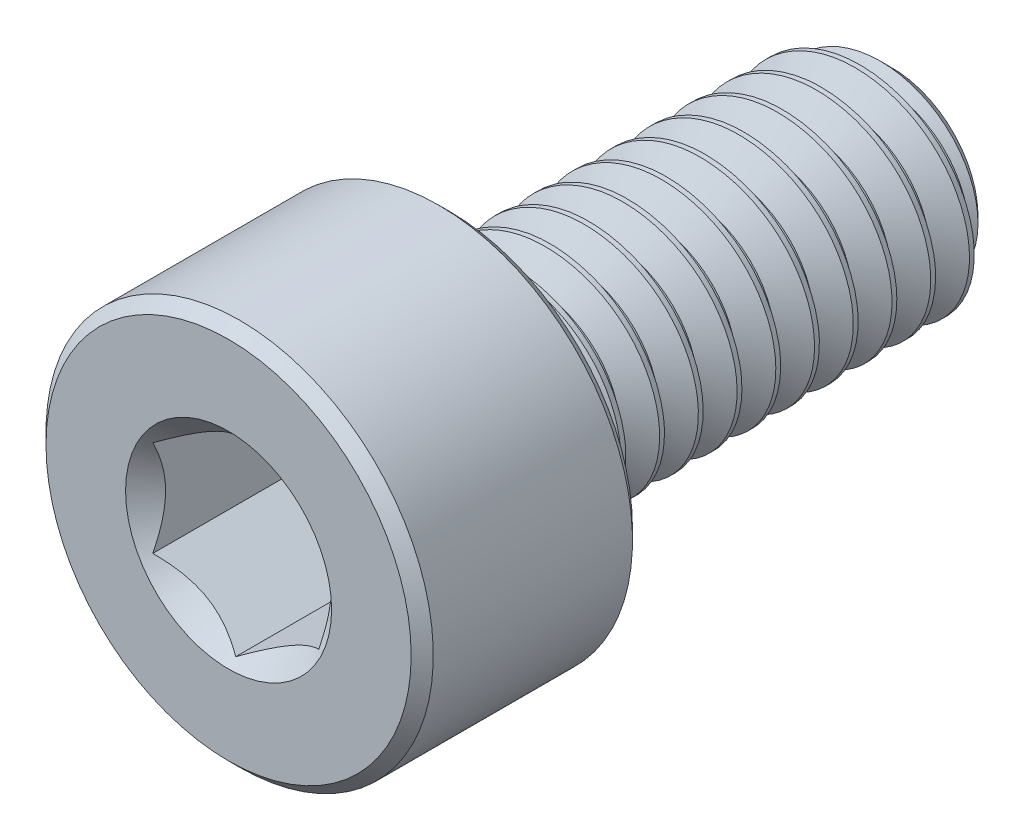
SolidWorks part; units mm, degrees
ref_plane "Front Plane" through (0, 0, 0) normal (0, 0, 1) x (1, 0, 0)
ref_plane "Top Plane" through (0, 0, 0) normal (0, 1, 0) x (1, 0, 0)
ref_plane "Right Plane" through (0, 0, 0) normal (1, 0, 0) x (0, 0, -1)
sketch "Sketch1" plane through (0, 0, 0) normal (1, 0, 0) x (0, 0, -1)
  line L0 (-6, 0) -> (6, 0) construction
  line L1 (6, 0) -> (6, 1.5453) construction
  line L2 (6, 1.5453) -> (5.5453, 2) construction
  line L3 (5.5453, 2) -> (5.475, 2) construction
  line L4 (5.475, 2) -> (-2, 2) construction
  line L5 (-2, 2) -> (-2, 3.5) construction
  line L6 (-2, 3.5) -> (-6, 3.5) construction
  line L7 (-6, 3.5) -> (-6, 0) construction
  line L8 (6, 1.5453) -> (6, 2) construction
  line L9 (5.9562, 2.0758) -> (6.3062, 1.4696) construction
  line L10 (6.3062, 1.4696) -> (6.6562, 2.0758) construction
  line L11 (6.6562, 2.0758) -> (5.9562, 2.0758) construction
  line L12 (6.3062, 2.0758) -> (6.3063, 2) construction
  line L13 (6.3062, 1.4696) -> (6.3062, 1.5453) construction
  line L14 (6.2625, 1.5453) -> (6.35, 1.5453) construction
  line L15 (6, 2) -> (6.6125, 2) construction
  line L16 (5.9781, 2.0379) -> (6.6344, 2.0379) construction
  line L17 (6, 0) -> (6, -2) construction
  line L18 (-2.2, 3.5) -> (-2, 3.3) construction
  line L19 (-5.8, 3.5) -> (-6, 3.3) construction
  line L20 (-2, 2) -> (-2, 0) construction
  line L21 (-2, 1) -> (0.6667, 1) construction
  line L22 (0.6667, 1) -> (3.3333, 1) construction
  line L23 (3.3333, 1) -> (6, 1) construction
  line L24 (0.6667, 1) -> (0.6667, 2) construction
  line L25 (0.6667, 2) -> (0.6667, 3.5) construction
  line L26 (3.3333, 1) -> (3.3333, 3.5) construction
  point P0 (-6, 1.5)
  point P3 (4.25, 2)
  point P4 (0, 0)
  point P18 (3.3333, 2)
  point P22 (6.3062, 1.5453)
  point P24 (5.475, 2)
  point P25 (6.3063, 2)
  point P28 (6.3063, 2.0379)
  point P29 (4.25, -2)
  point P30 (0.6667, 2)
  point P31 (-4, 3.5)
  point P37 (-2.7, 3.5)
  point P38 (-5.7, 3.5)
  point P45 (0.6667, 1)
  point P46 (3.3333, 1)
  dimension "D2" = 0.0875
  dimension "D7" = 0.2
  dimension "D8" = 0.2
  dimension "D9" = 0.2
  dimension "D10" = 0.1
  dimension "D11" = 0.5
  dimension "Drive Size" = 3
  dimension "Head Diameter" = 7
  dimension "Head Height" = 4
  dimension "Thread Pitch" = 0.7
  dimension "Thread Size" = 4
  dimension "Length" = 8
  dimension "D12" = 0.525
  dimension "D4" = 1.75
  dimension "D3" = 45
sketch "Sketch2" plane through (0, 0, 0) normal (1, 0, 0) x (0, 0, -1)
  line L0 (-6, 0) -> (-6, 3.3)
  line L1 (-5.8, 3.5) -> (-2.2, 3.5)
  line L2 (-2, 3.3) -> (-2, 2.2)
  line L4 (5.5453, 2) -> (6, 1.5453)
  line L5 (6, 1.5453) -> (6, 0)
  line L6 (-2, 3.5) -> (-6, 3.5) construction
  line L7 (6, 0) -> (-6, 0)
  line L8 (-5.8, 3.5) -> (-6, 3.3) construction
  line L10 (-5.8, 3.5) -> (-6, 3.3)
  line L14 (-2.2, 3.5) -> (-2, 3.3) construction
  line L16 (-2.2, 3.5) -> (-2, 3.3)
  line L17 (-2, 2) -> (-2, 3.5) construction
  line L19 (-1.8, 2) -> (5.5453, 2)
  line L20 (5.475, 2) -> (-2, 2) construction
  arc A1 (-2, 2.2) -> (-1.8, 2) centre (-1.8, 2.2) ccw
  dimension "D3" = 0.2
revolve "Revolve1" add sketch "Sketch2" angle 360 about L7
sketch "Sketch3" plane through (0, 0, 6) normal (0, 0, 1) x (1, 0, 0)
  line L1 (1.5, -0.866) -> (1.5, 0.866)
  line L2 (1.5, 0.866) -> (0, 1.7321)
  line L3 (0, 1.7321) -> (-1.5, 0.866)
  line L4 (-1.5, 0.866) -> (-1.5, -0.866)
  line L5 (-1.5, -0.866) -> (0, -1.7321)
  line L6 (0, -1.7321) -> (1.5, -0.866)
  circle A0 centre (0, 0) radius 1.5 construction
  circle A1 centre (0, 0) radius 3.5 construction
  circle A2 centre (0, 0) radius 3.5 construction
  circle A3 centre (0, 0) radius 1.7321 construction
  point P13 (0, 0)
  dimension "D1" = 3.4641
extrude "Cut-Extrude1" cut sketch "Sketch3" against normal offset from surface (3 mm away) 1 up to face at (0, 3.3, 2)
sketch "Sketch4" plane through (0, 0, 6) normal (0, 0, 1) x (1, 0, 0)
  circle A0 centre (0, 0) radius 1.862
  dimension "D1" = 3.7239
extrude "Cut-Extrude2" cut sketch "Sketch4" against normal up to vertex (2 mm away) draft 45 up to point (0, 3.5, 4)
sketch "Sketch11" plane through (0, 0, 0) normal (1, 0, 0) x (0, 0, -1)
  line L0 (-6, 0) -> (6, 0) construction
  line L1 (-6, 0) -> (6, 0) construction
  line L2 (-0.5, 0) -> (-0.5, 2) construction
  line L3 (5.475, 2) -> (-2, 2) construction
  line L4 (4.5, 0) -> (4.5, 2) construction
  line L6 (6, 1.5453) -> (6, 2) construction
  point P2 (-0.5, 0)
  point P3 (4.5, 0)
  dimension "D1" = 1.5
  dimension "D2" = 1.5
sketch "Sketch6" plane through (0, 0, -6) normal (0, 0, -1) x (-1, 0, 0)
  circle A0 centre (0, 0) radius 2
curve "Helix/Spiral1" pitch 0.7 height 8.7 radius 2 centre (0, 0, -6) axis (0, 0, 1) start towards (0, 1, 0)
sketch "Sketch10" plane through (0, 0, 0) normal (1, 0, 0) x (0, 0, -1)
  line L0 (-1.8, -3.5) -> (-1.8, 3.5)
  line L5 (-6, 0) -> (6, 0) construction
  line L6 (-1.8, 2) -> (-1.8, -2) construction
  point P3 (-1.8, 0)
split "Split1" trim tools "Sketch10" bodies to split 106 resulting bodies 114 115
sketch "Sketch7" plane through (0, 0, 0) normal (1, 0, 0) x (0, 0, -1)
  line L0 (5.9781, 2.0379) -> (6.6344, 2.0379)
  line L1 (6.6344, 2.0379) -> (6.35, 1.5453)
  line L2 (6.35, 1.5453) -> (6.2625, 1.5453)
  line L3 (6.2625, 1.5453) -> (5.9781, 2.0379)
sweep "Cut-Sweep1" cut profiles "Sketch7" path "Helix/Spiral1" align with end faces yes
sketch "Sketch8" plane through (0, 0, 0) normal (1, 0, 0) x (0, 0, -1)
  line L0 (-2, 0) -> (-2, 2)
  line L1 (-1.8, -2) -> (-1.8, 2) construction
  line L2 (-2, 2) -> (-1.8, 2)
  line L4 (-1.8, 2) -> (-0.6453, 0)
  line L5 (-0.6453, 0) -> (-2, 0)
  line L6 (5.475, 2) -> (-2, 2) construction
  line L7 (-6, 0) -> (6, 0) construction
  dimension "D1" = 60
revolve "Revolve2" add sketch "Sketch8" angle 360 about L5
equation "\"D2@Sketch1\" = \"Thread Pitch@Sketch1\" / 8"
equation "\"D4@Helix/Spiral1\" = \"Thread Pitch@Sketch1\""
equation "\"D7@Sketch1\" = \"Head Height@Sketch1\" * .05"
equation "\"D8@Sketch1\"=\"D7@Sketch1\""
equation "\"D9@Sketch1\"=\"D7@Sketch1\""
equation "\"D10@Sketch1\"=\"D7@Sketch1\"/2"
equation "\"D11@Sketch1\"=\"D10@Sketch1\"*5"
equation "\"D4@Sketch1\"=\"Thread Pitch@Sketch1\"*2.5"
equation "\"D12@Sketch1\"=\"Thread Pitch@Sketch1\"*.75"
equation "\"D3@Helix/Spiral1\"=\"Length@Sketch1\"+\"Thread Pitch@Sketch1\""
equation "\"D3@Sketch2\"=\"Thread Size@Sketch1\"*0.05"
equation "\"D1@Sketch11\"=\"Length@Sketch1\"*0.1875"
equation "\"D2@Sketch11\"=\"D1@Sketch11\""
equation "\"D1@Sketch4\"=\"D1@Sketch3\"*1.075"
